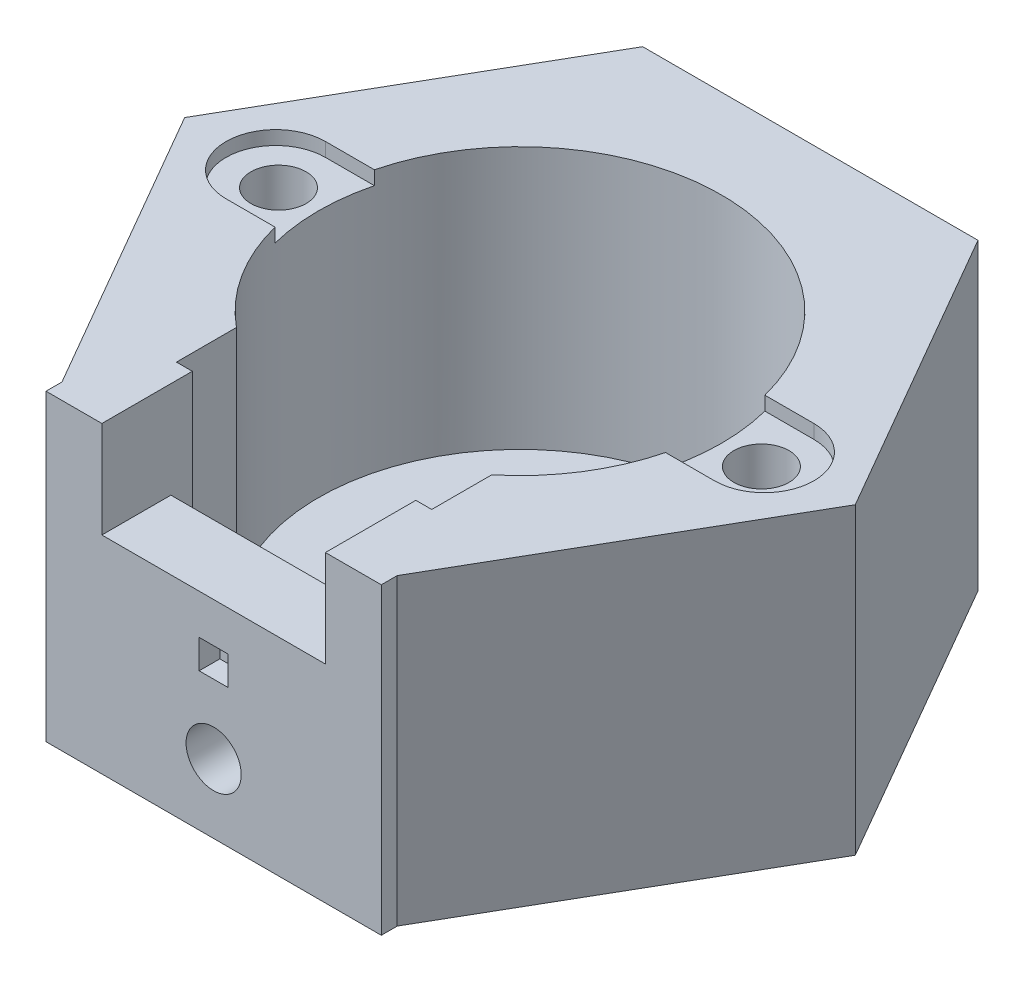
SolidWorks part; units mm, degrees
ref_plane "Front Plane" through (0, 0, 0) normal (0, 0, 1) x (1, 0, 0)
ref_plane "Top Plane" through (0, 0, 0) normal (0, 1, 0) x (1, 0, 0)
ref_plane "Right Plane" through (0, 0, 0) normal (1, 0, 0) x (0, 0, -1)
sketch "Sketch1" plane through (0, 0, 0) normal (0, 1, 0) x (1, 0, 0)
  line L0 (-33.6669, 0) -> (32.8036, 0) construction
  line L1 (0, 37.5104) -> (0, -35.9484) construction
  line L2 (-17.7, 3.6) -> (-14.1492, 3.6)
  line L3 (-17.7, -3.6) -> (-14.1492, -3.6)
  line L4 (14.1492, 3.6) -> (17.7, 3.6)
  line L5 (24.3, 0) -> (12.15, 21.0444)
  line L6 (12.15, 21.0444) -> (-12.15, 21.0444)
  line L7 (-12.15, 21.0444) -> (-24.3, 0)
  line L8 (-24.3, 0) -> (-12.15, -21.0444)
  line L9 (-12.15, -21.0444) -> (12.15, -21.0444)
  line L10 (12.15, -21.0444) -> (24.3, 0)
  line L12 (-8.1, -12.147) -> (-8.1, -22.2)
  line L13 (-8.1, -22.2) -> (8.1, -22.2)
  line L14 (8.1, -12.147) -> (8.1, -22.2)
  line L19 (14.1492, -3.6) -> (17.7, -3.6)
  line L20 (-8.1, -17.2) -> (8.1, -17.2)
  line L22 (-12.15, -22.2) -> (12.15, -22.2)
  line L23 (-12.15, -22.2) -> (-12.15, -21.0444)
  line L24 (-12.15, -21.0444) -> (12.15, -21.0444)
  line L25 (12.15, -22.2) -> (12.15, -21.0444)
  line L26 (-9.25, 0) -> (9.25, 0)
  line L27 (-9.25, 0) -> (-9.25, -15.647)
  line L28 (-9.25, -15.647) -> (9.25, -15.647)
  line L29 (9.25, 0) -> (9.25, -15.647)
  arc A0 (8.1, -12.147) -> (-8.1, -12.147) centre (0, 0) ccw
  arc A1 (17.7, -3.6) -> (17.7, 3.6) centre (17.7, 0) ccw
  arc A2 (-17.7, -3.6) -> (-17.7, 3.6) centre (-17.7, 0) cw
  circle A5 centre (0, 0) radius 21.0444 construction
  circle A6 centre (17.5, 0) radius 2
  circle A7 centre (-17.5, 0) radius 2
  dimension "D1" = 29.2
  dimension "D2" = 7.2
  dimension "D3" = 4
  dimension "D5" = 3
  dimension "D7" = 5
  dimension "D4" = 35.4
  dimension "D6" = 16.2
  dimension "D8" = 18.5
  dimension "D9" = 35
  dimension "D10" = 17.2
  dimension "D11" = 3.5
extrude "Boss-Extrude12" add sketch "Sketch1" along normal blind 22 contours L3 A2 L2 A0 L4 A1 L19 L14 L9 L10 L5 L6 L7 L8 L12 region at (-21.9429, 0, 0)
extrude "Boss-Extrude13" add sketch "Sketch1<14>" along normal blind 21 contours L19 A1 L4 A0 A6 | A2 L3 A0 L2 A7 region at (-15.9246, 0, -3.4985) region at (15.9246, 0, -3.4985)
sketch "Sketch1<14>" plane through (0, 0, 0) normal (0, 1, 0) x (1, 0, 0) same geometry as "Sketch1"
extrude "Boss-Extrude14" add sketch "Sketch1<15>" along normal blind 3 contours A0 region at (0, 0, -4.077)
sketch "Sketch1<15>" plane through (0, 0, 0) normal (0, 1, 0) x (1, 0, 0) same geometry as "Sketch1"
extrude "Boss-Extrude15" add sketch "Sketch1<16>" along normal blind 3 contours A0 L12 L20 L14 region at (0, 0, 16.4235)
sketch "Sketch1<16>" plane through (0, 0, 0) normal (0, 1, 0) x (1, 0, 0) same geometry as "Sketch1"
extrude "Boss-Extrude16" add sketch "Sketch1<17>" along normal blind 15 contours L20 L12 L9 L14 region at (0, 0, 19.1222)
sketch "Sketch1<17>" plane through (0, 0, 0) normal (0, 1, 0) x (1, 0, 0) same geometry as "Sketch1"
extrude "Boss-Extrude17" add sketch "Sketch1<18>" along normal blind 18 contours A6 | A7 region at (17.5, 0, 0) region at (-17.5, 0, 0)
sketch "Sketch1<18>" plane through (0, 0, 0) normal (0, 1, 0) x (1, 0, 0) same geometry as "Sketch1"
extrude "Boss-Extrude18" add sketch "Sketch1<19>" along normal blind 22 contours L23 L22 L12 L9 | L22 L25 L9 L14 region at (-10.125, 0, 21.6222) region at (10.125, 0, 21.6222)
sketch "Sketch1<19>" plane through (0, 0, 0) normal (0, 1, 0) x (1, 0, 0) same geometry as "Sketch1"
extrude "Boss-Extrude19" add sketch "Sketch1<20>" along normal blind 15 contours L14 L9 L12 L13 region at (0, 0, 21.6222)
sketch "Sketch1<20>" plane through (0, 0, 0) normal (0, 1, 0) x (1, 0, 0) same geometry as "Sketch1"
sketch "Sketch10" plane through (0, 0, 22.2) normal (0, 0, 1) x (1, 0, 0)
  line L0 (0, 36.7435) -> (0, -17.2864) construction
  line L2 (-12.15, 0) -> (12.15, 0) construction
  line L3 (-1.05, 12.1) -> (1.05, 12.1)
  line L4 (-1.05, 12.1) -> (-1.05, 10)
  line L5 (-1.05, 10) -> (1.05, 10)
  line L6 (1.05, 12.1) -> (1.05, 10)
  circle A0 centre (0, 5) radius 2
  dimension "D1" = 4
  dimension "D2" = 3
  dimension "D3" = 3
  dimension "D4" = 2.1
  dimension "D5" = 2.1
extrude "Cut-Extrude6" cut sketch "Sketch10" against normal blind 3 contours A0
extrude "Cut-Extrude7" cut sketch "Sketch10<10>" against normal blind 1.5 contours L5 L6 L3 L4
sketch "Sketch10<10>" plane through (0, 0, 22.2) normal (0, 0, 1) x (1, 0, 0) same geometry as "Sketch10"
extrude "Boss-Extrude20" add sketch "Sketch1<21>" along normal blind 3 contours L14 A0 L29 L26 L27 L12 L28 | A0 L27 L28 L12 | A0 L14 L28 L29 region at (-8.6958, 0, 13.6838) region at (0, 0, 7.6356) region at (8.6958, 0, 13.6838)
sketch "Sketch1<21>" plane through (0, 0, 0) normal (0, 1, 0) x (1, 0, 0) same geometry as "Sketch1"
sketch "Sketch13" plane through (0, 0, -21.0444) normal (0, 0, -1) x (-1, 0, 0)
  line L0 (0, 41.963) -> (0, -12.0669) construction
  line L1 (12.15, 22) -> (12.15, 0) construction
  line L3 (-1.05, 12.1) -> (1.05, 12.1)
  line L4 (-1.05, 12.1) -> (-1.05, 10)
  line L5 (-1.05, 10) -> (1.05, 10)
  line L6 (1.05, 12.1) -> (1.05, 10)
  line L7 (-12.15, 22) -> (-12.15, 0) construction
  line L9 (-12.15, 0) -> (12.15, 0) construction
  circle A0 centre (0, 5) radius 2
  dimension "D1" = 4
  dimension "D2" = 3
  dimension "D3" = 3
  dimension "D4" = 2.1
  dimension "D5" = 2.1
extrude "Cut-Extrude9" cut sketch "Sketch13" against normal blind 3 contours A0
extrude "Cut-Extrude10" cut sketch "Sketch13<13>" against normal blind 1.5
sketch "Sketch13<13>" plane through (0, 0, -21.0444) normal (0, 0, -1) x (-1, 0, 0) same geometry as "Sketch13"
